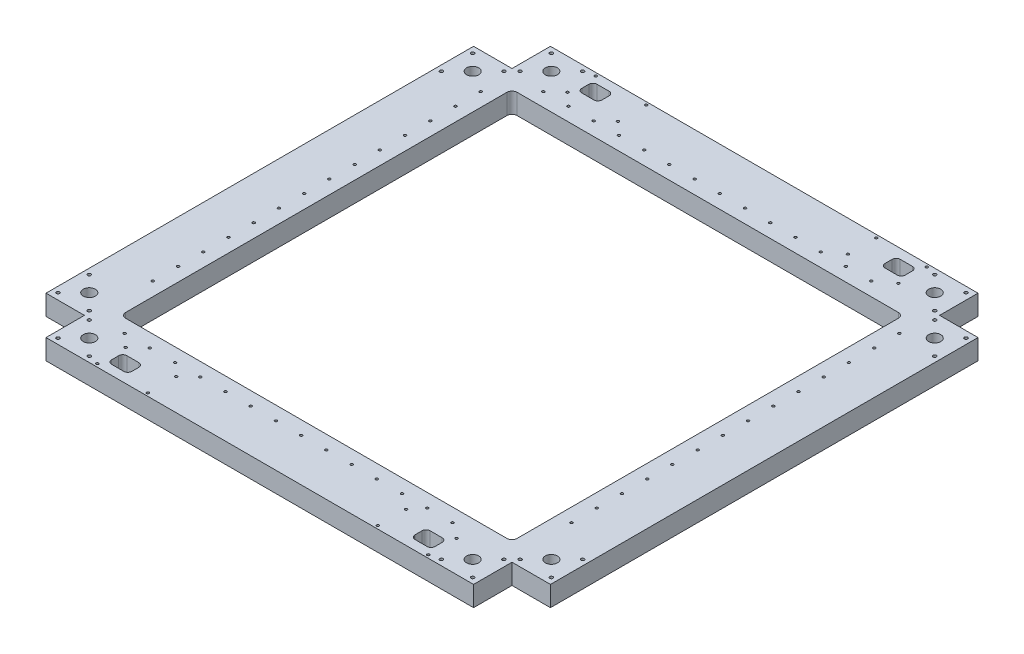
SolidWorks part; units mm, degrees
material "ASTM A36 Steel"
ref_plane "Front Plane" through (0, 0, 0) normal (0, 0, 1) x (1, 0, 0)
ref_plane "Top Plane" through (0, 0, 0) normal (0, 1, 0) x (1, 0, 0)
ref_plane "Right Plane" through (0, 0, 0) normal (1, 0, 0) x (0, 0, -1)
sketch "Sketch1" plane through (0, 0, 0) normal (0, 1, 0) x (1, 0, 0)
  line L1 (250, -250) -> (-250, -250)
  line L2 (250, -250) -> (250, 250)
  line L3 (250, 250) -> (-250, 250)
  line L4 (-250, -250) -> (-250, 250)
  line L5 (250, -250) -> (-250, 250) construction
  line L6 (250, 250) -> (-250, -250) construction
  point P0 (0, 0)
  dimension "D1" = 500
  dimension "D2" = 500
extrude "Boss-Extrude1" add sketch "Sketch1" along normal blind 20
sketch "Sketch2" plane through (0, 20, 0) normal (0, 1, 0) x (1, 0, 0)
  line L0 (250, 250) -> (-250, 250) construction
  line L10 (-250, 250) -> (-250, -250) construction
  line L15 (-250, 169) -> (-208, 169)
  line L16 (-250, 169) -> (-250, 211)
  line L17 (-174.5, 213.5) -> (-205.5, 213.5)
  line L27 (-250, 211) -> (-208, 211)
  line L33 (-208, 169) -> (-208, 211)
  line L35 (-250, 169) -> (-208, 211) construction
  line L36 (-250, 211) -> (-208, 169) construction
  line L37 (-169, 208) -> (-211, 208)
  line L38 (-169, 208) -> (-169, 250)
  line L39 (-169, 250) -> (-211, 250)
  line L40 (-211, 208) -> (-211, 250)
  line L41 (-169, 208) -> (-211, 250) construction
  line L42 (-169, 250) -> (-211, 208) construction
  line L43 (-208, 206) -> (-213, 211)
  line L44 (-174.5, 213.5) -> (-174.5, 244.5)
  line L45 (-174.5, 244.5) -> (-205.5, 244.5)
  line L46 (-205.5, 213.5) -> (-205.5, 244.5)
  line L47 (-174.5, 213.5) -> (-205.5, 244.5) construction
  line L48 (-174.5, 244.5) -> (-205.5, 213.5) construction
  line L49 (-213.5, 174.5) -> (-244.5, 174.5)
  line L50 (-213.5, 174.5) -> (-213.5, 205.5)
  line L51 (-213.5, 205.5) -> (-244.5, 205.5)
  line L52 (-244.5, 174.5) -> (-244.5, 205.5)
  line L53 (-213.5, 174.5) -> (-244.5, 205.5) construction
  line L54 (-213.5, 205.5) -> (-244.5, 174.5) construction
  line L55 (-206, 208) -> (-211, 213)
  line L56 (-213, 211) -> (-211, 213) construction
  point P1 (-229, 190)
  point P5 (-190, 229)
  point P23 (-229, 190)
  point P27 (-190, 229)
  dimension "D1" = 5
  dimension "D2" = 45
  dimension "D3" = 42
  dimension "D4" = 31
  dimension "D5" = 45
  dimension "D6" = 5
  dimension "D7" = 60
hole_wizard "Bearing Press Fit" positions "Sketch8" profile "Sketch9" hole size "Ø12.0" standard "ANSI Metric" end condition through all
sketch "Sketch8" plane through (0, 20, 0) normal (0, 1, 0) x (1, 0, 0)
  line L1 (-169, 250) -> (-211, 208) construction
  point P8 (-190, 229)
  point P12 (-229, 190)
sketch "Sketch9" plane through (-190, 20, -229) normal (1, 0, 0) x (0, 0, 1)
  line L0 (0, 0) -> (0, 20)
  line L1 (0, 20) -> (6, 20)
  line L2 (6, 20) -> (6, 0)
  line L5 (6, 0) -> (0, 0)
  line L11 (0, -6.35) -> (0, 107.95) construction
  dimension "Thru Hole Dia." = 12
  dimension "Thru Hole Depth" = 20
ref_axis "Axis1" through (0, 8.4, 0) along (0, -1, 0)
pattern_circular "CirPattern1" count 4 over 360 about axis through (0, 8.4, 0) along (0, -1, 0) of "Bearing Press Fit"
sketch "Sketch5" plane through (0, 20, 0) normal (0, 1, 0) x (1, 0, 0)
  line L1 (194, -194) -> (-194, -194)
  line L2 (194, -194) -> (194, 194)
  line L3 (194, 194) -> (-194, 194)
  line L4 (-194, -194) -> (-194, 194)
  line L5 (194, -194) -> (-194, 194) construction
  line L6 (194, 194) -> (-194, -194) construction
  point P0 (0, 0)
  dimension "D1" = 388
extrude "Cut-Extrude1" cut sketch "Sketch5" against normal up to surface (20 mm away) up to face at (-229, 0, 196)
sketch "Sketch10" plane through (0, 0, 0) normal (0, 1, 0) x (1, 0, 0)
  line L5 (194, 194) -> (-194, 194) construction
  line L6 (214, -214) -> (-214, -214)
  line L14 (214, -214) -> (214, 214)
  line L15 (214, 214) -> (-214, 214)
  line L16 (-214, -214) -> (-214, 214)
  line L17 (214, -214) -> (-214, 214) construction
  line L18 (214, 214) -> (-214, -214) construction
  line L19 (201.5, -201.5) -> (-201.5, -201.5)
  line L20 (201.5, -201.5) -> (201.5, 201.5)
  line L21 (201.5, 201.5) -> (-201.5, 201.5)
  line L22 (-201.5, -201.5) -> (-201.5, 201.5)
  line L23 (201.5, -201.5) -> (-201.5, 201.5) construction
  line L24 (201.5, 201.5) -> (-201.5, -201.5) construction
  point P0 (0, 0)
  point P6 (0, 0)
  dimension "D2" = 7.5
  dimension "D1" = 12.5
extrude "Linear Rail Slot" cut sketch "Sketch10" along normal blind 2.5
fillet "Fillet2" radius 5 4 edges at (-194, 10, 194) (194, 10, 194) (194, 10, -194) (-194, 10, -194)
sketch "Sketch11" plane through (0, 2.5, 0) normal (0, -1, 0) x (1, 0, 0)
  line L0 (-194, 207.5) -> (166, 207.5)
  line L1 (-201.5, 201.5) -> (201.5, 201.5) construction
  line L3 (-214, -214) -> (-214, 214) construction
  point P16 (148.5, 207.5)
  point P18 (123.5, 207.5)
  point P19 (98.5, 207.5)
  point P20 (73.5, 207.5)
  point P21 (48.5, 207.5)
  point P22 (23.5, 207.5)
  point P23 (-1.5, 207.5)
  point P24 (-26.5, 207.5)
  point P25 (-51.5, 207.5)
  point P26 (-76.5, 207.5)
  point P28 (-101.5, 207.5)
  point P29 (-126.5, 207.5)
  point P30 (-151.5, 207.5)
  point P31 (-176.5, 207.5)
  dimension "D1" = 360
  dimension "D2" = 6
  dimension "D4" = 14
  dimension "D5" = 25
  dimension "D6" = 20
  dimension "D3" = 17.5
hole_wizard "Tap Drill for M3x0.5 Tap1" positions "Sketch12" profile "Sketch13" hole size "M3x0.5" standard "ANSI Metric" end condition through all
sketch "Sketch12" plane through (0, 2.5, 0) normal (0, -1, 0) x (-1, 0, 0)
  line L0 (194, -207.5) -> (-166, -207.5) construction
  point P28 (-148.5, -207.5)
  point P31 (-123.5, -207.5)
  point P34 (-98.5, -207.5)
  point P37 (-73.5, -207.5)
  point P40 (-48.5, -207.5)
  point P43 (-23.5, -207.5)
  point P46 (1.5, -207.5)
  point P49 (26.5, -207.5)
  point P51 (51.5, -207.5)
  point P54 (76.5, -207.5)
  point P57 (101.5, -207.5)
  point P61 (126.5, -207.5)
  point P64 (151.5, -207.5)
  point P67 (176.5, -207.5)
sketch "Sketch13" plane through (148.5, 2.5, 207.5) normal (1, 0, 0) x (0, 0, -1)
  line L0 (0, 0) -> (0, 17.5)
  line L1 (0, 17.5) -> (1.25, 17.5)
  line L2 (1.25, 17.5) -> (1.25, 0)
  line L5 (1.25, 0) -> (0, 0)
  line L11 (0, -6.35) -> (0, 107.95) construction
  dimension "Thru Hole Dia." = 2.5
  dimension "Thru Hole Depth" = 17.5
sketch "Sketch14" plane through (0, 0, 0) normal (0, -1, 0) x (1, 0, 0)
  line L1 (-151.5, 213.5) -> (-176.5, 213.5)
  line L2 (-147.5, 217.5) -> (-147.5, 219.5)
  line L3 (-151.5, 223.5) -> (-176.5, 223.5)
  line L4 (-180.5, 217.5) -> (-180.5, 219.5)
  line L5 (-147.5, 213.5) -> (-180.5, 223.5) construction
  line L6 (-147.5, 223.5) -> (-180.5, 213.5) construction
  line L7 (-201.5, 201.5) -> (201.5, 201.5) construction
  line L8 (-176.5, 207.5) -> (-151.5, 207.5) construction
  line L19 (-1.5, 213.5) -> (-26.5, 213.5)
  line L25 (2.5, 217.5) -> (2.5, 219.5)
  line L26 (-1.5, 223.5) -> (-26.5, 223.5)
  line L31 (-30.5, 217.5) -> (-30.5, 219.5)
  line L32 (2.5, 213.5) -> (-30.5, 223.5) construction
  line L33 (2.5, 223.5) -> (-30.5, 213.5) construction
  line L34 (-26.5, 207.5) -> (-1.5, 207.5) construction
  line L35 (148.5, 213.5) -> (123.5, 213.5)
  line L36 (152.5, 217.5) -> (152.5, 219.5)
  line L37 (148.5, 223.5) -> (123.5, 223.5)
  line L38 (119.5, 217.5) -> (119.5, 219.5)
  line L39 (152.5, 213.5) -> (119.5, 223.5) construction
  line L40 (152.5, 223.5) -> (119.5, 213.5) construction
  line L41 (123.5, 207.5) -> (148.5, 207.5) construction
  arc A3 (-147.5, 219.5) -> (-151.5, 223.5) centre (-151.5, 219.5) ccw
  arc A4 (-151.5, 213.5) -> (-147.5, 217.5) centre (-151.5, 217.5) ccw
  arc A5 (-176.5, 213.5) -> (-180.5, 217.5) centre (-176.5, 217.5) cw
  arc A6 (-176.5, 223.5) -> (-180.5, 219.5) centre (-176.5, 219.5) ccw
  arc A7 (2.5, 219.5) -> (-1.5, 223.5) centre (-1.5, 219.5) ccw
  arc A8 (-1.5, 213.5) -> (2.5, 217.5) centre (-1.5, 217.5) ccw
  arc A9 (-26.5, 213.5) -> (-30.5, 217.5) centre (-26.5, 217.5) cw
  arc A10 (-26.5, 223.5) -> (-30.5, 219.5) centre (-26.5, 219.5) ccw
  arc A11 (152.5, 219.5) -> (148.5, 223.5) centre (148.5, 219.5) ccw
  arc A12 (148.5, 213.5) -> (152.5, 217.5) centre (148.5, 217.5) ccw
  arc A13 (123.5, 213.5) -> (119.5, 217.5) centre (123.5, 217.5) cw
  arc A14 (123.5, 223.5) -> (119.5, 219.5) centre (123.5, 219.5) ccw
  point P0 (-164, 218.5)
  point P12 (-164, 207.5)
  point P26 (-14, 218.5)
  point P45 (136, 218.5)
  dimension "D5" = 3
  dimension "D4" = 4
  dimension "D1" = 33
  dimension "D2" = 12
  dimension "D3" = 10
  dimension "D7" = 25
  dimension "D6" = 150
mirror "Mirror5" about plane through (0, 0, 0) normal (0, 0, 1) of "Tap Drill for M3x0.5 Tap1"
ref_plane "Plane1" through (0, 0, 0) normal (-0.7071, 0, 0.7071) x (0.7071, 0, 0.7071)
mirror "Mirror6" about plane through (0, 0, 0) normal (-0.7071, 0, 0.7071) of "Mirror5"
sketch "Sketch19" plane through (0, 2.5, 0) normal (0, -1, 0) x (1, 0, 0)
  line L0 (-198.5, 201.5) -> (-198.5, 214)
  line L1 (-201.5, 201.5) -> (201.5, 201.5) construction
  line L2 (-214, 214) -> (214, 214) construction
  line L3 (-198.5, 214) -> (-214, 214)
  line L4 (-214, 214) -> (-214, 198.5)
  line L5 (-214, -214) -> (-214, 214) construction
  line L6 (-214, 198.5) -> (-201.5, 198.5)
  line L7 (-201.5, -201.5) -> (-201.5, 201.5) construction
  line L8 (-201.5, 198.5) -> (-201.5, 201.5)
  line L9 (-201.5, 201.5) -> (-198.5, 201.5)
  dimension "D1" = 3
extrude "Boss-Extrude2" add sketch "Sketch19" along normal up to surface (2.5 mm away) up to face at (-229, 0, 196)
pattern_circular "CirPattern4" count 4 over 360 about axis through (0, 8.4, 0) along (0, -1, 0) of "Boss-Extrude2"
sketch "Sketch20" plane through (0, 20, 0) normal (0, 1, 0) x (1, 0, 0)
  line L5 (-250, -250) -> (250, -250) construction
  line L20 (140.3, -225.5) -> (160.3, -240.5) construction
  line L23 (160.3, -225.5) -> (140.3, -240.5) construction
  line L28 (114, -247) -> (164, -219) construction
  line L29 (164, -247) -> (114, -219) construction
  line L30 (164, -219) -> (114, -219) construction
  line L31 (114, -247) -> (114, -219) construction
  line L32 (164, -247) -> (114, -247) construction
  line L33 (164, -247) -> (164, -219) construction
  line L34 (156.3, -240.5) -> (144.3, -240.5)
  line L35 (140.3, -229.5) -> (140.3, -236.5)
  line L36 (156.3, -225.5) -> (144.3, -225.5)
  line L37 (160.3, -229.5) -> (160.3, -236.5)
  arc A12 (144.3, -225.5) -> (140.3, -229.5) centre (144.3, -229.5) ccw
  arc A13 (140.3, -236.5) -> (144.3, -240.5) centre (144.3, -236.5) ccw
  arc A14 (160.3, -236.5) -> (156.3, -240.5) centre (156.3, -236.5) cw
  arc A15 (160.3, -229.5) -> (156.3, -225.5) centre (156.3, -229.5) ccw
  circle A16 centre (190, -229) radius 6 construction
  point P8 (150.3, -233)
  point P9 (0, 0)
  point P10 (0, 0)
  point P11 (0, 0)
  point P12 (0, 0)
  point P13 (0, 0)
  point P14 (0, 0)
  point P15 (0, 0)
  point P16 (0, 0)
  point P17 (0, 0)
  point P18 (0, 0)
  point P19 (0, 0)
  point P65 (150.3, -233)
  point P66 (139, -233)
  point P67 (139, -233)
  dimension "D7" = 39.7
  dimension "D8" = 11.3
  dimension "D6" = 4
  dimension "D1" = 28
  dimension "D2" = 50
  dimension "D3" = 17
  dimension "D4" = 20
  dimension "D5" = 15
extrude "Cut-Extrude3" cut sketch "Sketch20" against normal through all
hole_wizard "Tap Drill for M3x0.5 Tap3" positions "Sketch28" profile "Sketch29" hole size "M3x0.5" standard "ANSI Metric" end condition through all
sketch "Sketch28" plane through (0, 20, 0) normal (0, 1, 0) x (1, 0, 0)
  point P0 (164, -219)
  point P3 (164, -247)
  point P6 (114, -247)
  point P8 (114, -219)
  point P12 (114, -247)
sketch "Sketch29" plane through (164, 20, 219) normal (1, 0, 0) x (0, 0, 1)
  line L0 (0, 0) -> (0, 20)
  line L1 (0, 20) -> (1.25, 20)
  line L2 (1.25, 20) -> (1.25, 0)
  line L5 (1.25, 0) -> (0, 0)
  line L11 (0, -6.35) -> (0, 107.95) construction
  dimension "Thru Hole Dia." = 2.5
  dimension "Thru Hole Depth" = 20
mirror "Mirror8" about plane through (0, 0, 0) normal (1, 0, 0) of "Tap Drill for M3x0.5 Tap3", "Cut-Extrude3"
mirror "Mirror9" about plane through (0, 0, 0) normal (0, 0, 1) of "Mirror8"
sketch "Sketch24" plane through (0, 20, 0) normal (0, 1, 0) x (1, 0, 0)
  line L1 (244.5, -205.5) -> (213.5, -205.5)
  line L2 (244.5, -205.5) -> (244.5, -174.5)
  line L3 (244.5, -174.5) -> (213.5, -174.5)
  line L4 (213.5, -205.5) -> (213.5, -174.5)
  line L5 (244.5, -205.5) -> (213.5, -174.5) construction
  line L6 (244.5, -174.5) -> (213.5, -205.5) construction
  line L7 (205.5, -244.5) -> (174.5, -244.5)
  line L8 (205.5, -244.5) -> (205.5, -213.5)
  line L9 (205.5, -213.5) -> (174.5, -213.5)
  line L10 (174.5, -244.5) -> (174.5, -213.5)
  line L11 (205.5, -244.5) -> (174.5, -213.5) construction
  line L12 (205.5, -213.5) -> (174.5, -244.5) construction
  point P0 (229, -190)
  point P6 (190, -229)
  dimension "D1" = 31
hole_wizard "M3 Clearance Hole1" positions "Sketch25" profile "Sketch26" hole size "M3" standard "ANSI Metric" end condition through all
sketch "Sketch25" plane through (0, 20, 0) normal (0, 1, 0) x (1, 0, 0)
  point P0 (205.5, -244.5)
  point P3 (205.5, -213.5)
  point P9 (174.5, -244.5)
  point P12 (213.5, -205.5)
  point P18 (244.5, -174.5)
  point P21 (244.5, -205.5)
  point P26 (0, 0)
  point P27 (0, 0)
sketch "Sketch26" plane through (205.5, 20, 244.5) normal (1, 0, 0) x (0, 0, 1)
  line L0 (0, 0) -> (0, 20)
  line L1 (0, 20) -> (1.6, 20)
  line L2 (1.6, 20) -> (1.6, 0)
  line L5 (1.6, 0) -> (0, 0)
  line L11 (0, -6.35) -> (0, 107.95) construction
  dimension "Thru Hole Dia." = 3.2
  dimension "Thru Hole Depth" = 20
sketch "Sketch27" plane through (0, 20, 0) normal (0, 1, 0) x (1, 0, 0)
  line L1 (250, -250) -> (211.9, -250)
  line L2 (250, -250) -> (250, -211.9)
  line L3 (250, -211.9) -> (211.9, -211.9)
  line L4 (211.9, -250) -> (211.9, -211.9)
  dimension "D1" = 38.1
extrude "Cut-Extrude4" cut sketch "Sketch27" against normal up to surface (20 mm away) up to face at (205.5, 0, 246.1)
pattern_circular "CirPattern3" count 4 over 360 about axis through (0, 8.4, 0) along (0, -1, 0) of "M3 Clearance Hole1", "Cut-Extrude4"
fillet "Fillet5" radius 4 16 edges at (198.5, 1.25, 214) (198.5, 1.25, 201.5) (201.5, 1.25, 198.5) (214, 1.25, 198.5) (-214, 1.25, 198.5) (-198.5, 1.25, 214) (-201.5, 1.25, 198.5) (-198.5, 1.25, 201.5) (-214, 1.25, -198.5) (-198.5, 1.25, -214) (-198.5, 1.25, -201.5) (-201.5, 1.25, -198.5) (198.5, 1.25, -201.5) (198.5, 1.25, -214) (201.5, 1.25, -198.5) (214, 1.25, -198.5)
